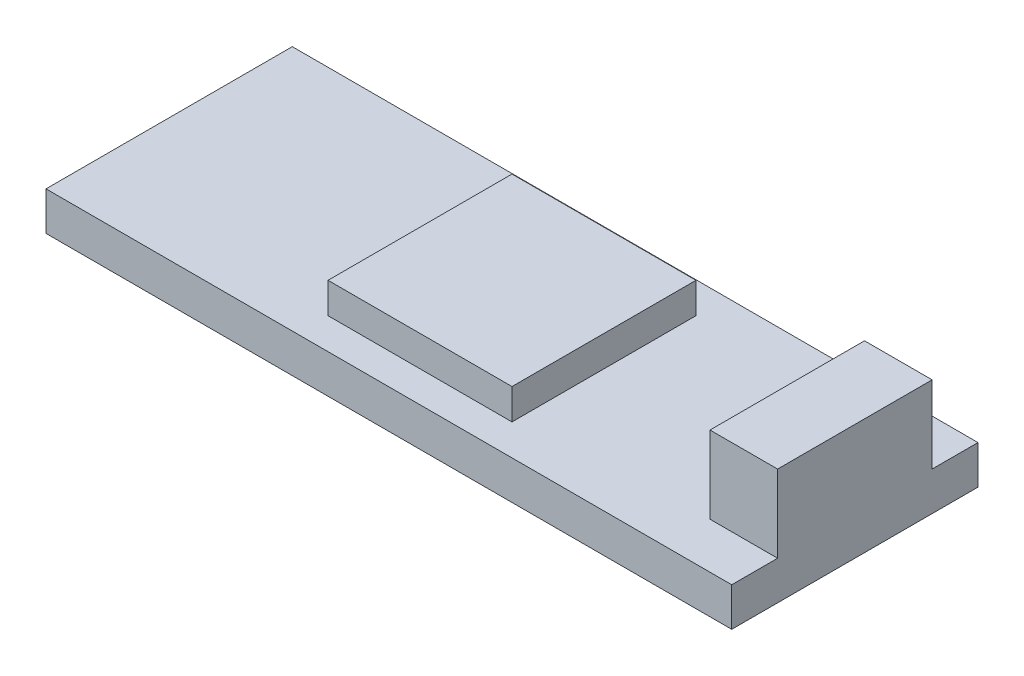
SolidWorks part; units mm, degrees
ref_plane "Front Plane" through (0, 0, 0) normal (0, 0, 1) x (1, 0, 0)
ref_plane "Top Plane" through (0, 0, 0) normal (0, 1, 0) x (1, 0, 0)
ref_plane "Right Plane" through (0, 0, 0) normal (1, 0, 0) x (0, 0, -1)
sketch "Sketch1" plane through (0, 0, 0) normal (0, 1, 0) x (1, 0, 0)
  line L1 (-35.5, -12.75) -> (35.5, -12.75)
  line L2 (-35.5, -12.75) -> (-35.5, 12.75)
  line L3 (-35.5, 12.75) -> (35.5, 12.75)
  line L4 (35.5, -12.75) -> (35.5, 12.75)
  line L5 (-35.5, -12.75) -> (35.5, 12.75) construction
  line L6 (-35.5, 12.75) -> (35.5, -12.75) construction
  point P0 (0, 0)
  dimension "D1" = 71
  dimension "D2" = 25.5
extrude "Boss-Extrude2" add sketch "Sketch1" along normal blind 4
sketch "Sketch4" plane through (0, 4, 0) normal (0, 1, 0) x (1, 0, 0)
  line L0 (-35.5, 0) -> (35.5, 0) construction
  line L1 (35.5, -12.75) -> (35.5, 12.75) construction
  line L3 (28.5, -8) -> (35.5, -8)
  line L4 (28.5, -8) -> (28.5, 8)
  line L5 (28.5, 8) -> (35.5, 8)
  line L6 (35.5, -8) -> (35.5, 8)
  line L7 (28.5, -8) -> (35.5, 8) construction
  line L8 (28.5, 8) -> (35.5, -8) construction
  point P0 (32, 0)
  point P6 (0, 0)
  dimension "D1" = 16
  dimension "D2" = 7
extrude "Boss-Extrude3" add sketch "Sketch4" along normal blind 8
sketch "Sketch5" plane through (0, 4, 0) normal (0, 1, 0) x (1, 0, 0)
  line L1 (-9.525, -9.525) -> (9.525, -9.525)
  line L2 (-9.525, -9.525) -> (-9.525, 9.525)
  line L3 (-9.525, 9.525) -> (9.525, 9.525)
  line L4 (9.525, -9.525) -> (9.525, 9.525)
  line L5 (-9.525, -9.525) -> (9.525, 9.525) construction
  line L6 (-9.525, 9.525) -> (9.525, -9.525) construction
  point P0 (0, 0)
  dimension "D1" = 19.05
  dimension "D2" = 19.05
extrude "Boss-Extrude4" add sketch "Sketch5" along normal blind 3.174
